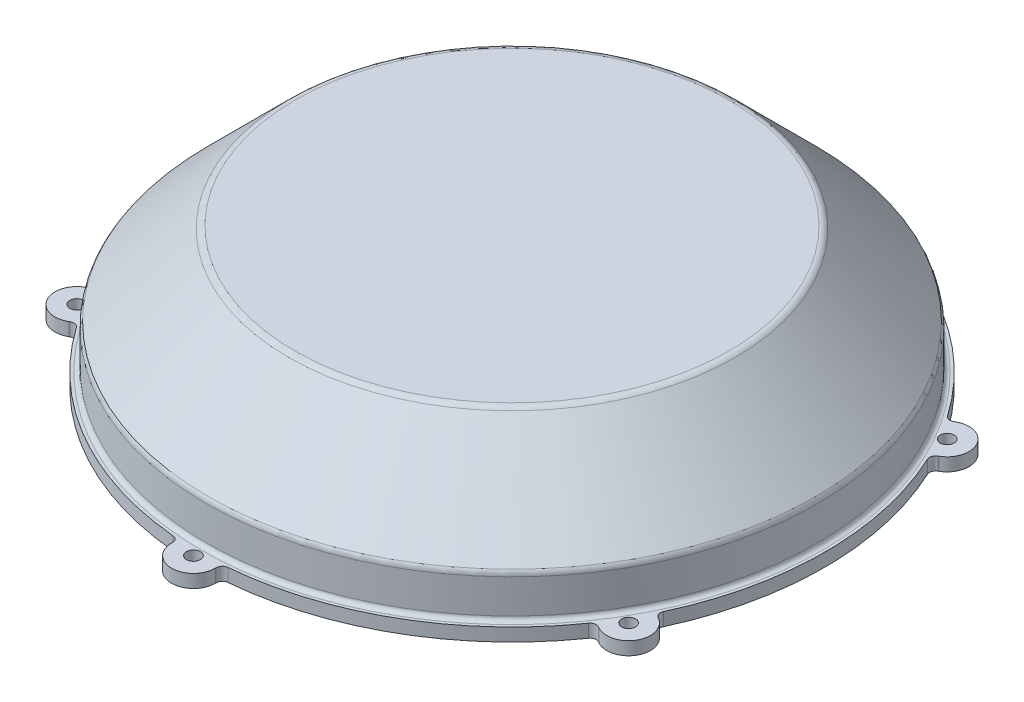
SolidWorks part; units mm, degrees
material "АБС-2020, черный"
ref_plane "Спереди" through (0, 0, 0) normal (0, 0, 1) x (1, 0, 0)
ref_plane "Сверху" through (0, 0, 0) normal (0, 1, 0) x (1, 0, 0)
ref_plane "Справа" through (0, 0, 0) normal (1, 0, 0) x (0, 0, -1)
other "Configuration Table"
sketch "Эскиз1" plane through (0, 0, 0) normal (0, 1, 0) x (1, 0, 0)
  circle A0 centre (0, 0) radius 70
  circle A1 centre (0, 0) radius 67.5
  dimension "D1" = 140
  dimension "D2" = 135
extrude "Бобышка-Вытянуть1" add sketch "Эскиз1" along normal blind 10
sketch "Эскиз2" plane through (0, 0, 0) normal (0, -1, 0) x (1, 0, 0)
  line L0 (0, 0) -> (0, 68.2261) construction
  line L1 (-5, 73) -> (-5, 72.7838)
  line L2 (60.7199, 40.8301) -> (60.5327, 40.722)
  line L3 (5, 72.7838) -> (5, 73)
  line L4 (0, 69.7236) -> (0, 91.161) construction
  line L5 (65.5327, 32.0618) -> (65.7199, 32.1699)
  line L6 (65.7199, -32.1699) -> (65.5327, -32.0618)
  line L7 (60.5327, -40.722) -> (60.7199, -40.8301)
  line L8 (5, -73) -> (5, -72.7838)
  line L9 (-5, -72.7838) -> (-5, -73)
  line L10 (-60.7199, -40.8301) -> (-60.5327, -40.722)
  line L11 (-65.5327, -32.0618) -> (-65.7199, -32.1699)
  line L12 (-65.7199, 32.1699) -> (-65.5327, 32.0618)
  line L13 (-60.5327, 40.722) -> (-60.7199, 40.8301)
  line L14 (0, 0) -> (63.2199, 36.5) construction
  line L15 (63.2199, 36.5) -> (63.2199, -36.5) construction
  line L16 (63.2199, -36.5) -> (0, 0) construction
  line L17 (0, 0) -> (0, -73) construction
  line L18 (0, -73) -> (-63.2199, -36.5) construction
  line L19 (-63.2199, -36.5) -> (0, 0) construction
  line L20 (0, 0) -> (-63.2199, 36.5) construction
  arc A0 (5, 73) -> (-5, 73) centre (0, 73) ccw
  circle A1 centre (0, 0) radius 67.5
  arc A2 (-6.2774, 71.3892) -> (-58.6862, 41.131) centre (0, 0) ccw
  circle A3 centre (0, 73) radius 1.6
  arc A4 (65.7199, 32.1699) -> (60.7199, 40.8301) centre (63.2199, 36.5) ccw
  circle A5 centre (63.2199, 36.5) radius 1.6
  arc A6 (60.7199, -40.8301) -> (65.7199, -32.1699) centre (63.2199, -36.5) ccw
  circle A7 centre (63.2199, -36.5) radius 1.6
  arc A8 (-5, -73) -> (5, -73) centre (0, -73) ccw
  circle A9 centre (0, -73) radius 1.6
  arc A10 (-65.7199, -32.1699) -> (-60.7199, -40.8301) centre (-63.2199, -36.5) ccw
  circle A11 centre (-63.2199, -36.5) radius 1.6
  arc A12 (-60.7199, 40.8301) -> (-65.7199, 32.1699) centre (-63.2199, 36.5) ccw
  circle A13 centre (-63.2199, 36.5) radius 1.6
  arc A14 (58.6862, 41.131) -> (6.2774, 71.3892) centre (0, 0) ccw
  arc A15 (64.9636, -30.2583) -> (64.9636, 30.2583) centre (0, 0) ccw
  arc A16 (-58.6862, -41.131) -> (-6.2774, -71.3892) centre (0, 0) ccw
  arc A17 (6.2774, -71.3892) -> (58.6862, -41.131) centre (0, 0) ccw
  arc A18 (-64.9636, 30.2583) -> (-64.9636, -30.2583) centre (0, 0) ccw
  arc A19 (-5, 72.7838) -> (-6.2774, 71.3892) centre (-6.4, 72.7838) cw
  arc A20 (-60.5327, 40.722) -> (-58.6862, 41.131) centre (-59.8327, 41.9345) ccw
  arc A21 (-65.5327, 32.0618) -> (-64.9636, 30.2583) centre (-66.2327, 30.8494) cw
  arc A22 (-65.5327, -32.0618) -> (-64.9636, -30.2583) centre (-66.2327, -30.8494) ccw
  arc A23 (-60.5327, -40.722) -> (-58.6862, -41.131) centre (-59.8327, -41.9345) cw
  arc A24 (-5, -72.7838) -> (-6.2774, -71.3892) centre (-6.4, -72.7838) ccw
  arc A25 (5, -72.7838) -> (6.2774, -71.3892) centre (6.4, -72.7838) cw
  arc A26 (60.5327, -40.722) -> (58.6862, -41.131) centre (59.8327, -41.9345) ccw
  arc A27 (65.5327, -32.0618) -> (64.9636, -30.2583) centre (66.2327, -30.8494) cw
  arc A28 (65.5327, 32.0618) -> (64.9636, 30.2583) centre (66.2327, 30.8494) ccw
  arc A29 (60.5327, 40.722) -> (58.6862, 41.131) centre (59.8327, 41.9345) cw
  arc A30 (6.2774, 71.3892) -> (5, 72.7838) centre (6.4, 72.7838) cw
  point P45 (0, 0)
  dimension "D1" = 10
  dimension "D2" = 3.2
  dimension "D4" = 1.4
  dimension "D3" = 135
  dimension "D6" = 60
  dimension "D5" = 73
  dimension "D7" = 60
  dimension "D8" = 60
  dimension "D9" = 60
extrude "Бобышка-Вытянуть2" add sketch "Эскиз2" along normal blind 3
fillet "Скругление1" radius 1 1 edges at (0, 0, -70)
sketch "Эскиз3" plane through (0, 0, 0) normal (0, 0, 1) x (1, 0, 0)
  line L0 (-69.5846, 10) -> (-50.5846, 29)
  line L1 (-50.5846, 29) -> (0, 29)
  line L2 (0, 29) -> (0, 27)
  line L3 (0, 27) -> (-49.7562, 27)
  line L4 (-49.7562, 27) -> (-66.7562, 10)
  line L5 (67.5, 10) -> (-67.5, 10) construction
  line L6 (-66.7562, 10) -> (-69.5846, 10)
  line L7 (70, 10) -> (-70, 10) construction
  line L8 (0, 27) -> (0, 0) construction
  dimension "D1" = 45
  dimension "D2" = 19
  dimension "D3" = 2
  dimension "D4" = 2
revolve "Повернуть1" add sketch "Эскиз3" angle 360 about L8
fillet "Скругление2" radius 2 2 edges at (-50.5846, 29, 0) (0, 10, 70)
